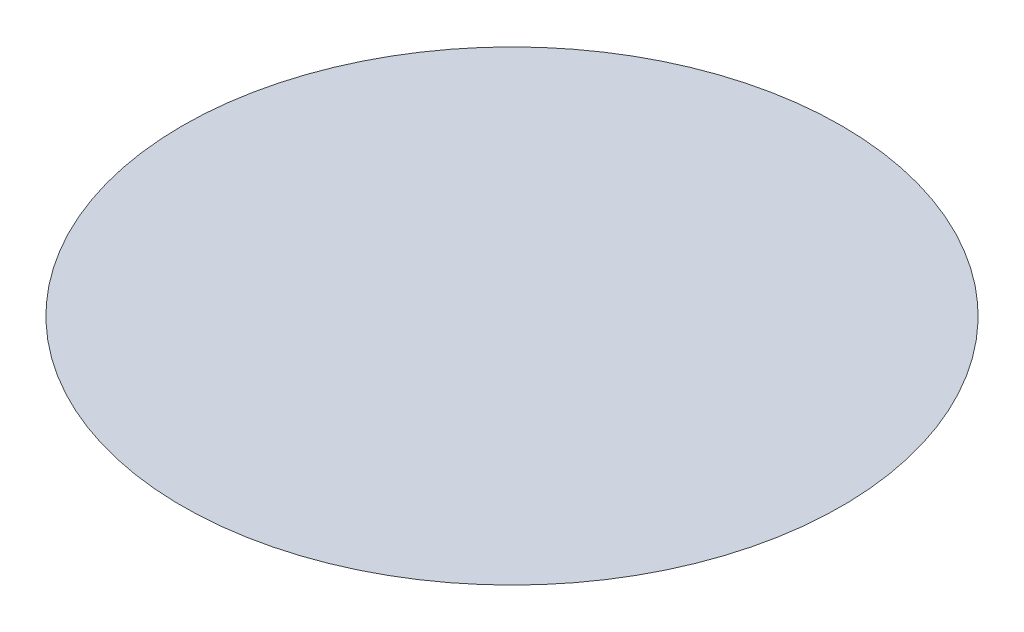
SolidWorks part; units mm, degrees
material "Alloy Steel"
ref_plane "Front Plane" through (0, 0, 0) normal (0, 0, 1) x (1, 0, 0)
ref_plane "Top Plane" through (0, 0, 0) normal (0, 1, 0) x (1, 0, 0)
ref_plane "Right Plane" through (0, 0, 0) normal (1, 0, 0) x (0, 0, -1)
sketch "Sketch1" plane through (0, 0, 0) normal (0, 0, 1) x (1, 0, 0)
  line L0 (0, 0) -> (0, 28.5)
  line L1 (0, 28.5) -> (102.9037, 28.5)
  arc A0 (0, 0) -> (102.9037, 28.5) centre (0, 200.025) ccw
  dimension "D1" = 200.025
  dimension "D2" = 28.5
revolve "Revolve1" add sketch "Sketch1" angle 360 about L0
